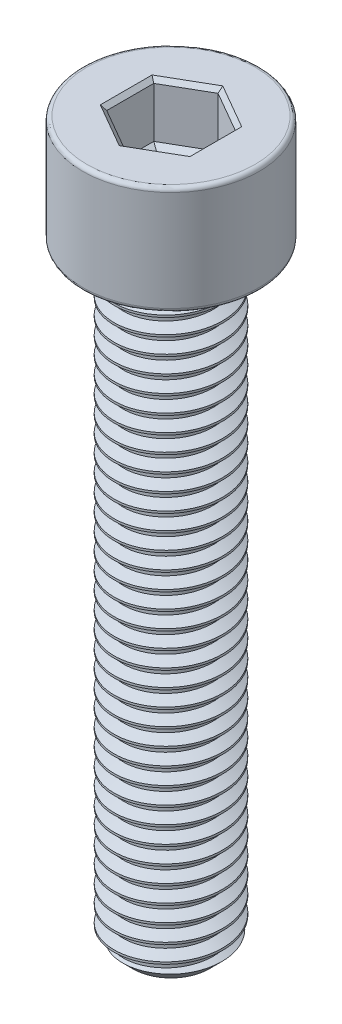
SolidWorks part; units mm, degrees
material "AISI Type A2 Tool Steel"
ref_plane "Front Plane" through (0, 0, 0) normal (0, 0, 1) x (1, 0, 0)
ref_plane "Top Plane" through (0, 0, 0) normal (0, 1, 0) x (1, 0, 0)
ref_plane "Right Plane" through (0, 0, 0) normal (1, 0, 0) x (0, 0, -1)
sketch "Sketch1" plane through (0, 0, 0) normal (0, 1, 0) x (1, 0, 0)
  circle A0 centre (0, 0) radius 4
  dimension "D1" = 8
extrude "Boss-Extrude1" add sketch "Sketch1" along normal blind 45
thread "Thread1" pitch 1.25 profile "Thread Profile1" start angle 0, offset 1.25, length 0, pitch 1.25, diameter 8
ref_plane "Plane1" through (-4, 46.25, 0) normal (0, 0, 1) x (-1, 0, 0)
sketch "Thread Profile1" plane through (-4, 46.25, 0) normal (0, 0, 1) x (-1, 0, 0)
  line L0 (0, 0) -> (0, 1.25) construction
  line L11 (0, 0) -> (0, 1.0937)
  line L12 (0, 1.0937) -> (-0.6766, 0.7031)
  line L13 (-0.6766, 0.7031) -> (-0.6766, 0.3906)
  line L15 (-0.6766, 0.3906) -> (0, 0)
  line L17 (-0.6766, 0.5469) -> (0, 0.5469) construction
  point P2 (0, 0)
  dimension "Pitch" = 1.25
  dimension "Profile_Angle" = 60
  dimension "Profile_Land" = 0.3125
  dimension "Profile_Height" = 0.6766
sketch "Sketch2" plane through (0, 45, 0) normal (0, 1, 0) x (1, 0, 0)
  circle A0 centre (0, 0) radius 6.5
  dimension "D1" = 13
extrude "Boss-Extrude2" add sketch "Sketch2" along normal blind 8
sketch "Sketch5" plane through (0, 0, 0) normal (0, 0, 1) x (1, 0, 0)
  line L0 (0, 0) -> (0, 0.9986) construction
  line L1 (0, 0) -> (4.01, 0) construction
  line L2 (4.01, 0) -> (4.01, 1.2)
  line L3 (4.01, 1.2) -> (2.81, 0)
  line L4 (2.81, 0) -> (4.01, 0)
  dimension "D1" = 1.2
  dimension "D2" = 45
  dimension "D3" = 4.01
revolve "Cut-Revolve1" cut sketch "Sketch5" angle 360 about L0
fillet "Fillet1" radius 0.3 2 edges at (0, 53, 6.5) (0, 45, 6.5)
sketch "Sketch6" plane through (0, 53, 0) normal (0, 1, 0) x (1, 0, 0)
  line L1 (0, 3.4641) -> (-3, 1.7321)
  line L2 (-3, 1.7321) -> (-3, -1.7321)
  line L3 (-3, -1.7321) -> (0, -3.4641)
  line L4 (0, -3.4641) -> (3, -1.7321)
  line L5 (3, -1.7321) -> (3, 1.7321)
  line L6 (3, 1.7321) -> (0, 3.4641)
  circle A0 centre (0, 0) radius 3 construction
  dimension "D1" = 6
extrude "Cut-Extrude1" cut sketch "Sketch6" against normal blind 4
chamfer "Chamfer1" distance 0.3 angle 45 6 edges at (-3, 53, 0) (-1.5, 53, 2.5981) (1.5, 53, 2.5981) (3, 53, 0) (1.5, 53, -2.5981) (-1.5, 53, -2.5981)
sketch "Sketch7" plane through (0, 49, 0) normal (0, 1, 0) x (1, 0, 0)
  line L1 (0, 3.4641) -> (-3, 1.7321)
  line L2 (-3, 1.7321) -> (-3, -1.7321)
  line L3 (-3, -1.7321) -> (0, -3.4641)
  line L4 (0, -3.4641) -> (3, -1.7321)
  line L5 (3, -1.7321) -> (3, 1.7321)
  line L6 (3, 1.7321) -> (0, 3.4641)
  circle A0 centre (0, 0) radius 3 construction
extrude "Cut-Extrude2" cut sketch "Sketch7" against normal blind 0.4 draft 60
